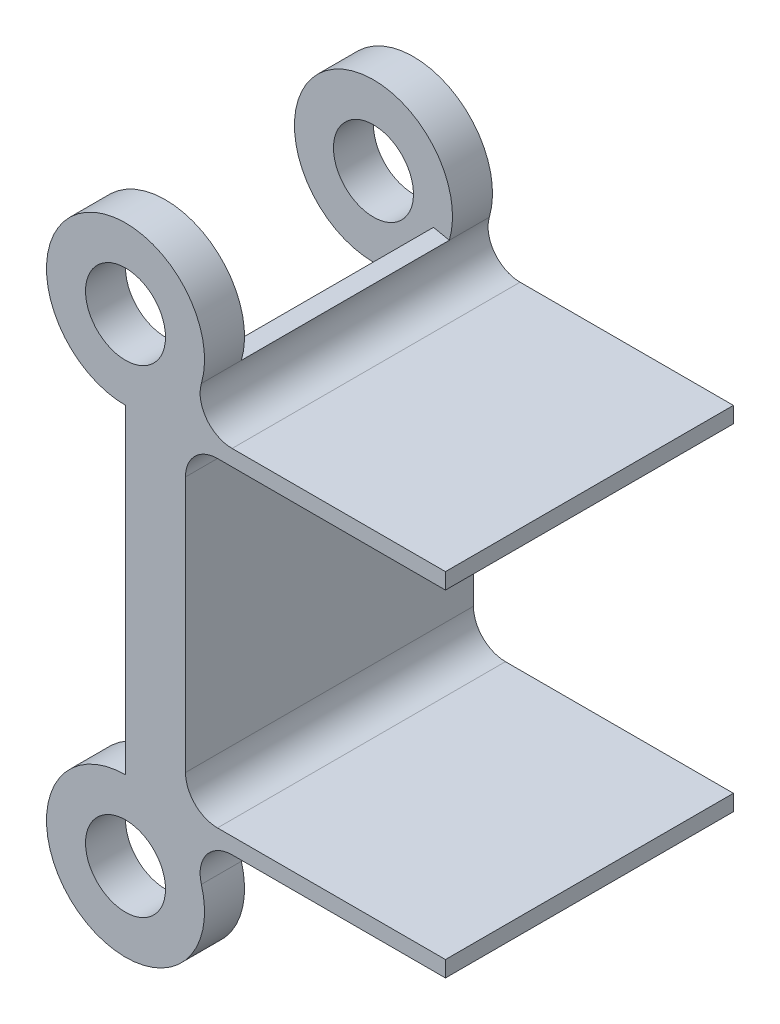
SolidWorks part; units mm, degrees
ref_plane "Front Plane" through (0, 0, 0) normal (0, 0, 1) x (1, 0, 0)
ref_plane "Top Plane" through (0, 0, 0) normal (0, 1, 0) x (1, 0, 0)
ref_plane "Right Plane" through (0, 0, 0) normal (1, 0, 0) x (0, 0, -1)
sketch "Sketch1" plane through (0, 0, 0) normal (0, 0, 1) x (1, 0, 0)
  circle A0 centre (0, 0) radius 3.175
  circle A1 centre (0, 0) radius 6.2738
  dimension "D1" = 6.35
  dimension "D2" = 12.5476
extrude "Boss-Extrude1" add sketch "Sketch1" along normal blind 22.86
ref_plane "Plane1" through (0, 6.2738, 0) normal (0, 1, 0) x (1, 0, 0)
sketch "Sketch2" plane through (0, 6.2738, 0) normal (0, 1, 0) x (1, 0, 0)
  line L0 (-6.2738, -22.86) -> (6.2738, -22.86) construction
  line L1 (0, -22.86) -> (25.4, -22.86)
  line L2 (0, -22.86) -> (0, 0)
  line L3 (0, 0) -> (25.4, 0)
  line L4 (25.4, -22.86) -> (25.4, 0)
  line L5 (6.2738, 0) -> (-6.2738, 0) construction
  dimension "D1" = 25.4
extrude "Boss-Extrude2" add sketch "Sketch2" against normal blind 1.27
fillet "Fillet1" radius 2.54 1 edges at (3.7845, 5.0038, 11.43)
ref_plane "Plane2" through (0, 0, 3.175) normal (0, 0, -1) x (-1, 0, 0)
sketch "Sketch3" plane through (0, 0, 3.175) normal (0, 0, -1) x (-1, 0, 0)
  circle A3 centre (0, 0) radius 6.2738
extrude "Cut-Extrude1" cut sketch "Sketch3" against normal blind 16.51
sketch "Sketch4" [suppressed] plane through (0, 0, 3.175) normal (0, 0, -1) x (-1, 0, 0)
  circle A0 centre (0, 0) radius 6.2738
  circle A1 centre (0, 0) radius 3.175
  arc A2 (-6.0237, 1.7538) -> (0, 6.2738) centre (0, 0) ccw construction
  dimension "D1" = 6.35
extrude "Boss-Extrude3" [suppressed] add sketch "Sketch4" against normal blind 19.05
sketch "Sketch6" [suppressed] plane through (0, 0, 0) normal (0, 0, -1) x (-1, 0, 0)
  circle A0 centre (0, 0) radius 6.2738
extrude "Cut-Extrude2" [suppressed] cut sketch "Sketch6" against normal blind 3.175
sketch "Sketch7" [suppressed] plane through (0, 0, 22.86) normal (0, 0, 1) x (1, 0, 0)
  circle A0 centre (0, 0) radius 6.2738
extrude "Cut-Extrude3" [suppressed] cut sketch "Sketch7" against normal blind 3.175
ref_plane "Plane3" [suppressed] through (0, 0, 6.35) normal (0, 0, -1) x (-1, 0, 0)
ref_plane "Plane4" [suppressed] through (0, 0, 3.175) normal (0, 0, -1) x (-1, 0, 0)
sketch "Sketch8" [suppressed] plane through (0, 0, 6.35) normal (0, 0, -1) x (-1, 0, 0)
  line L0 (-8.4624, 5.0038) -> (-3.7845, 5.0038)
  line L1 (-8.4624, 5.0038) -> (-6.2738, 0)
  arc A0 (-6.2738, 0) -> (-3.7845, 5.0038) centre (0, 0) ccw
extrude "Cut-Extrude4" [suppressed] cut sketch "Sketch8" against normal blind 10.16
sketch "Sketch9" plane through (0, 0, 19.685) normal (0, 0, -1) x (-1, 0, 0)
  line L0 (-6.2738, 0) -> (-8.4624, 5.0038)
  line L1 (-8.4624, 5.0038) -> (-3.7845, 5.0038)
  arc A0 (-6.2738, 0) -> (-3.7845, 5.0038) centre (0, 0) ccw
  arc A1 (-6.0237, 1.7538) -> (0, 6.2738) centre (0, 0) ccw construction
extrude "Cut-Extrude5" cut sketch "Sketch9" along normal blind 10.16 from offset 3.175
sketch "Sketch10" plane through (0, 0, 22.86) normal (0, 0, 1) x (1, 0, 0)
  line L0 (0, 6.2738) -> (0, 19.05)
  line L2 (4.7625, 4.084) -> (4.7625, 19.05)
  line L3 (4.7625, 19.05) -> (0, 19.05)
  arc A0 (0, 6.2738) -> (6.0237, 1.7538) centre (0, 0) ccw construction
  arc A1 (4.7625, 4.084) -> (0, 6.2738) centre (0, 0) ccw
  dimension "D1" = 19.05
  dimension "D2" = 4.7625
extrude "Boss-Extrude4" add sketch "Sketch10" against normal up to surface (22.86 mm away) contours L2 L3 L0 A1 up to face at (11.5393, 3.1773, 0)
fillet "Fillet2" radius 2.54 1 edges at (4.7625, 6.2738, 11.43)
mirror "Mirror5" about plane through (4.7625, 19.05, -15.7055) normal (0, 1, 0) of "Boss-Extrude4"
ref_plane "Plane5" through (0, 18.9738, 0) normal (0, 1, 0) x (1, 0, 0)
mirror "Mirror7" about plane through (0, 18.9738, 0) normal (0, 1, 0) of "Boss-Extrude1"
mirror "Mirror9" about plane through (0, 18.9738, 0) normal (0, 1, 0) of "Boss-Extrude2"
mirror "Mirror11" about plane through (0, 18.9738, 0) normal (0, 1, 0) of "Cut-Extrude1"
fillet "Fillet3" radius 2.54 1 edges at (4.7625, 31.6738, 11.43)
sketch "Sketch12" plane through (0, 0, 22.86) normal (0, 0, 1) x (1, 0, 0)
  line L1 (8.4624, 32.9438) -> (4.7625, 32.9438)
  line L2 (4.7625, 32.9438) -> (4.7625, 36.4518)
  line L4 (4.7625, 36.4518) -> (6.0237, 36.1938)
  arc A1 (4.7625, 33.8636) -> (0, 31.6738) centre (0, 37.9476) ccw construction
  arc A2 (6.0237, 36.1938) -> (8.4624, 32.9438) centre (8.4624, 35.4838) ccw
  point P1 (6.0237, 36.1938)
  point P2 (0, 0)
  point P6 (6.0237, 36.1938)
  point P15 (0, 0)
extrude "Boss-Extrude5" add sketch "Sketch12" against normal up to surface (22.86 mm away) up to face at (9.7212, 18.9828, 0)
